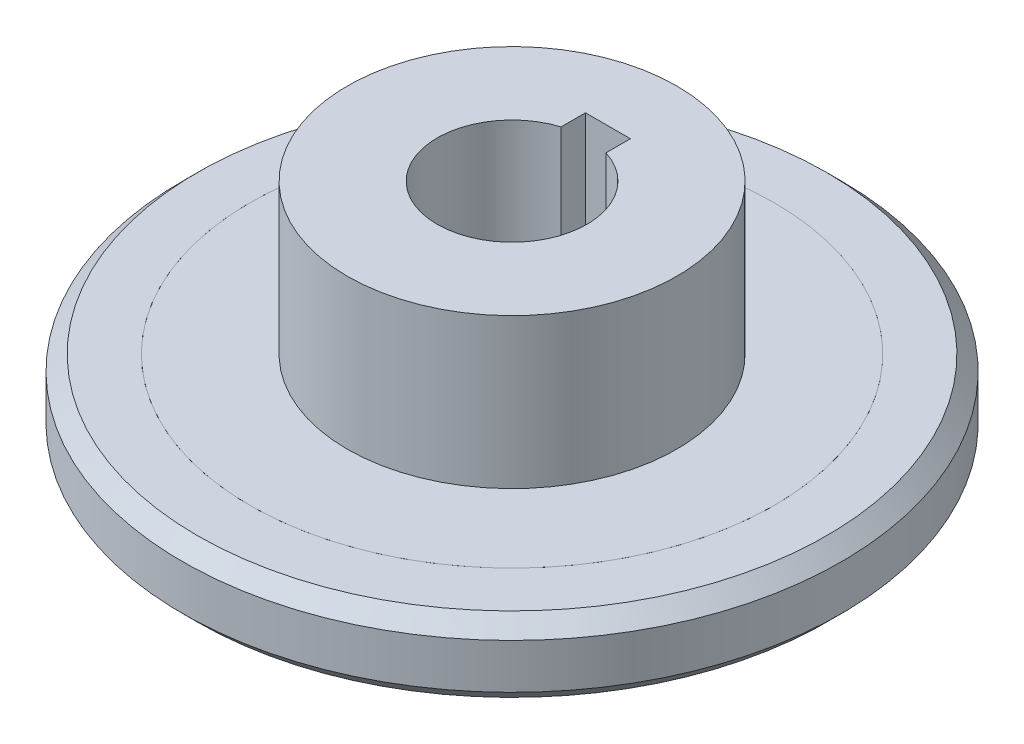
SolidWorks part; units mm, degrees
ref_plane "Front" through (0, 0, 0) normal (0, 0, 1) x (1, 0, 0)
ref_plane "Top" through (0, 0, 0) normal (0, 1, 0) x (1, 0, 0)
ref_plane "Right" through (0, 0, 0) normal (1, 0, 0) x (0, 0, -1)
sketch "Эскиз1" plane through (0, 0, 0) normal (0, 0, 1) x (1, 0, 0)
  line L0 (0, 0) -> (0, 6.9221) construction
  line L1 (5, 15) -> (5, 0)
  line L2 (5, 0) -> (17.5, 0)
  line L3 (17.5, 0) -> (17.5, 5)
  line L4 (17.5, 5) -> (11, 5)
  line L5 (11, 5) -> (11, 15)
  line L6 (11, 15) -> (5, 15)
  line L7 (1.3983, 5) -> (1.3983, 15) construction
  dimension "D1" = 35
  dimension "D2" = 10
  dimension "D3" = 5
  dimension "D5" = 22
revolve "Повернуть1" add sketch "Эскиз1" angle 360 about L0
sketch "Эскиз2" plane through (0, 0, 0) normal (0, 0, 1) x (1, 0, 0)
  line L3 (1.5, -27.4214) -> (-1.5, -27.4214)
  line L4 (1.5, -27.4214) -> (1.5, 27.4214)
  line L5 (1.5, 27.4214) -> (-1.5, 27.4214)
  line L6 (-1.5, -27.4214) -> (-1.5, 27.4214)
  line L7 (1.5, -27.4214) -> (-1.5, 27.4214) construction
  line L8 (1.5, 27.4214) -> (-1.5, -27.4214) construction
  point P0 (0, 0)
  dimension "D1" = 3
extrude "Вырез-Вытянуть1" cut sketch "Эскиз2" against normal blind 6.4
sketch "Эскиз3" plane through (0, 0, 0) normal (0, 0, 1) x (1, 0, 0)
  line L0 (0, 0) -> (0, 23.7771) construction
  line L1 (17.5, 0) -> (17.5, 5)
  line L2 (17.5, 0) -> (17.5, 5) construction
  line L3 (17.5, 5) -> (21, 5)
  line L6 (21, 5) -> (22, 4)
  line L7 (21, 0) -> (22, 1)
  line L8 (22, 1) -> (22, 4)
  line L11 (21, 0) -> (17.5, 0)
  line L12 (-17.5, 0) -> (17.5, 0) construction
  dimension "D1" = 45
  dimension "D2" = 1
  dimension "D3" = 44
revolve "Повернуть-Тонкостенный1" add sketch "Эскиз3" angle 360 about L0 wall 0.0001
sketch "Эскиз4" plane through (0, 5, 0) normal (0, 1, 0) x (1, 0, 0)
  circle A0 centre (-16.25, 0) radius 1.5
  circle A1 centre (16.25, 0) radius 1.5
  circle A2 centre (0, 0) radius 16.25 construction
  circle A3 centre (0, 0) radius 16.25 construction
  dimension "D3" = 3
extrude "Вырез-Вытянуть2" [suppressed] cut sketch "Эскиз4" against normal through all
